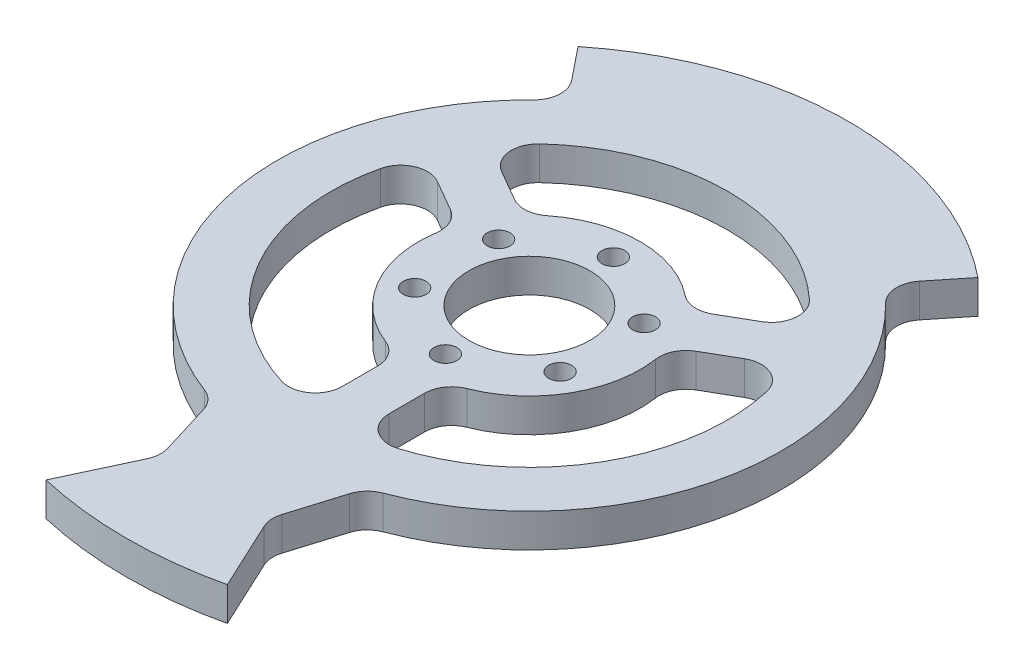
SolidWorks part; units mm, degrees
material "AISI Type A2 Tool Steel"
ref_plane "Front Plane" through (0, 0, 0) normal (0, 0, 1) x (1, 0, 0)
ref_plane "Top Plane" through (0, 0, 0) normal (0, 1, 0) x (1, 0, 0)
ref_plane "Right Plane" through (0, 0, 0) normal (1, 0, 0) x (0, 0, -1)
other "Center of Mass"
other "Bounding Box"
ref_plane "Default Plane" through (0, 2.286, 19.05) normal (0, -1, 0) x (-1, 0, 0)
sketch "Sketch1" plane through (0, 0, 0) normal (0, 1, 0) x (1, 0, 0)
  line L0 (0, -76.2) -> (0, -47.625) construction
  line L1 (0, -47.625) -> (0, -11.43) construction
  line L2 (0, -11.43) -> (0, 0) construction
  circle A0 centre (0, 0) radius 76.2 construction
  circle A1 centre (0, 0) radius 11.43
  arc A2 (0, -47.625) -> (0, 47.625) centre (0, 0) ccw
  arc A3 (0, 47.625) -> (0, -76.2) centre (0, -14.2875) ccw construction
  arc A4 (0, 47.625) -> (0, -47.625) centre (0, 0) ccw
  dimension "D1" = 152.4
  dimension "D2" = 22.86
  dimension "D3" = 95.25
extrude "Boss-Extrude2" add sketch "Sketch1" along normal mid plane 6.35
sketch "Sketch9" plane through (0, 3.175, 0) normal (0, 1, 0) x (1, 0, 0)
  line L2 (-17.1413, -74.247) -> (-10.241, -59.4494)
  line L3 (17.1413, -74.247) -> (10.241, -59.4494)
  line L4 (0, -76.2) -> (0, 0) construction
  line L5 (-10.241, -59.4494) -> (-14.5525, -45.3472)
  line L6 (10.241, -59.4494) -> (14.5525, -45.3472)
  line L7 (-37.8101, 47.0053) -> (-29.8501, 37.1095)
  line L8 (37.8101, 47.0053) -> (29.8501, 37.1095)
  line L9 (0, 60.325) -> (0, 0) construction
  line L10 (-10.241, -59.4494) -> (0, -37.4874) construction
  line L11 (0, -37.4874) -> (10.241, -59.4494) construction
  line L12 (-17.1413, -74.247) -> (0, 0) construction
  arc A5 (-17.1413, -74.247) -> (17.1413, -74.247) centre (0, 0) ccw
  arc A6 (-10.241, -59.4494) -> (10.241, -59.4494) centre (0, 0) ccw construction
  circle A7 centre (0, 0) radius 47.625 construction
  arc A8 (-14.5525, -45.3472) -> (14.5525, -45.3472) centre (0, 0) ccw
  arc A9 (-37.8101, 47.0053) -> (37.8101, 47.0053) centre (0, 0) cw
  arc A10 (29.8501, 37.1095) -> (-29.8501, 37.1095) centre (0, 0) ccw
  dimension "D1" = 76.2
  dimension "D3" = 12.7
  dimension "D5" = 13
  dimension "D2" = 12
  dimension "D4" = 77.625
  dimension "D6" = 17
extrude "Boss-Extrude4" add sketch "Sketch9" against normal through all
sketch "Sketch6" plane through (0, 3.175, 0) normal (0, 1, 0) x (1, 0, 0)
  line L0 (-29.994, 22.4497) -> (-15.5121, 14.0886)
  line L1 (15.5121, 14.0886) -> (29.994, 22.4497)
  line L2 (0, 0) -> (-32.2165, 18.6002) construction
  line L3 (0, 0) -> (32.2165, 18.6002) construction
  line L4 (-29.994, 22.4497) -> (-32.2165, 18.6002) construction
  line L5 (29.994, 22.4497) -> (32.2165, 18.6002) construction
  line L6 (0, 0) -> (0, 47.625) construction
  arc A0 (-15.5121, 14.0886) -> (15.5121, 14.0886) centre (0, 0) cw
  arc A1 (-29.994, 22.4497) -> (29.994, 22.4497) centre (0, 0) cw
  circle A2 centre (0, 0) radius 11.43 construction
  arc A4 (-4.6224, -47.4002) -> (-33.3394, 34.0092) centre (0, 0) ccw construction
  arc A5 (14.5525, -45.3472) -> (29.8501, 37.1095) centre (0, 0) ccw construction
  dimension "D3" = 60
  dimension "D4" = 10.16
  dimension "D1" = 9.525
  dimension "D2" = 4.445
  dimension "D5" = 60
extrude "Cut-Extrude2" cut sketch "Sketch6" against normal through all
pattern_circular "CirPattern1" count 3 over 360 about axis through (0, 3.175, 0) along (0, -1, 0) of "Cut-Extrude2"
sketch "Sketch7" [suppressed] plane through (0, 6.35, 0) normal (0, 1, 0) x (1, 0, 0)
  line L0 (12.4559, 70.0208) -> (11.1213, 62.5185)
  line L1 (70.0208, -12.4559) -> (62.5185, -11.1213)
  line L2 (0, 0) -> (52.0712, 36.3433) construction
  line L3 (0, 0) -> (0, 63.5) construction
  line L4 (-6.2364, -4.3527) -> (0, 0) construction
  arc A0 (70.0208, -12.4559) -> (12.4559, 70.0208) centre (0, 0) ccw
  arc A1 (2.4423, -63.453) -> (0, 63.5) centre (0, 0) ccw construction
  arc A2 (62.5185, -11.1213) -> (11.1213, 62.5185) centre (0, 0) ccw
  dimension "D1" = 7.62
  dimension "D3" = 90
sketch "Sketch10" plane through (0, 3.175, 0) normal (0, 1, 0) x (1, 0, 0)
  line L0 (0, 20.955) -> (0, 15.875) construction
  line L1 (0, 15.875) -> (0, 11.43) construction
  circle A0 centre (0, 15.875) radius 2.159
  circle A1 centre (0, 15.875) radius 3.9624 construction
  circle A2 centre (0, 0) radius 11.43 construction
  arc A3 (4.445, -20.4781) -> (19.9571, 6.3896) centre (0, 0) ccw construction
  dimension "D1" = 4.318
  dimension "D2" = 7.9248
  dimension "D3" = 15.875
extrude "Cut-Extrude3" cut sketch "Sketch10" against normal through all
pattern_circular "CirPattern8" count 6 over 360 about axis through (0, 3.175, 0) along (0, -1, 0) of "Cut-Extrude3" reverse direction yes
fillet "Fillet3" radius 5.08 12 edges at (-29.994, 0, -22.4497) (29.994, 0, -22.4497) (15.5121, 0, -14.0886) (-15.5121, 0, -14.0886) (4.445, 0, 37.2004) (34.439, 0, -14.7507) (19.9571, 0, -6.3896) (4.445, 0, 20.4781) (-4.445, 0, 37.2004) (-4.445, 0, 20.4781) (-19.9571, 0, -6.3896) (-34.439, 0, -14.7507)
other "Center of Mass Reference Point2"
fillet "Fillet4" radius 5.08 6 edges at (-10.241, 0, 59.4494) (-14.5525, 0, 45.3472) (10.241, 0, 59.4494) (14.5525, 0, 45.3472) (29.8501, 0, -37.1095) (-29.8501, 0, -37.1095)
equation "\"Unit Measure\"= \"BoundingVolume\" / \"Thickness\"'in^2"
